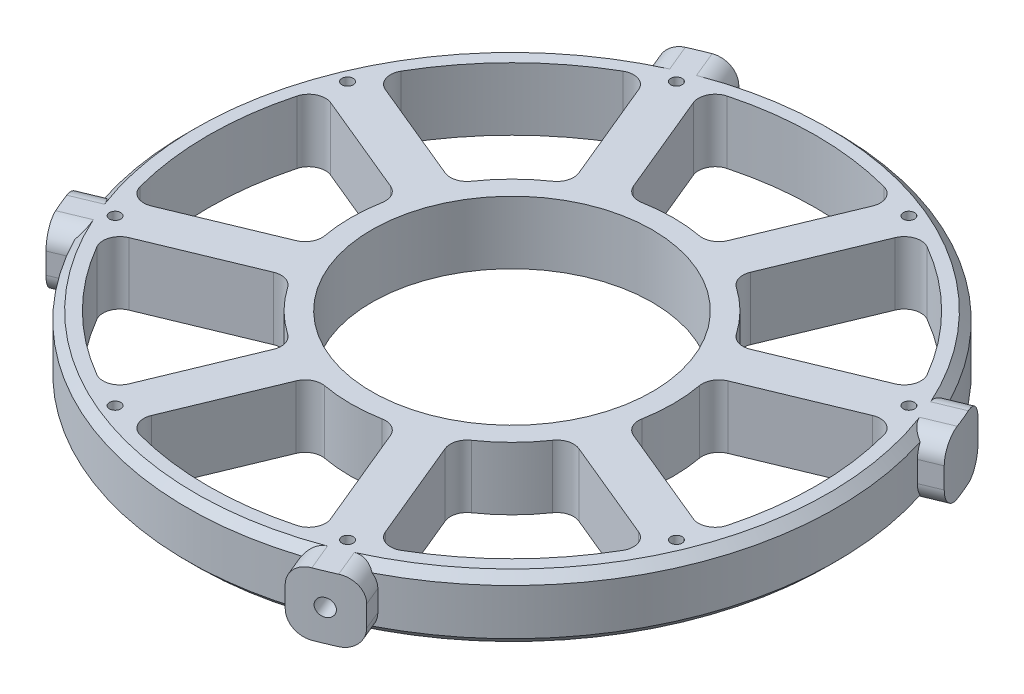
SolidWorks part; units mm, degrees
material "6061-T6 (SS)"
ref_plane "Front Plane" through (0, 0, 0) normal (0, 0, 1) x (1, 0, 0)
ref_plane "Top Plane" through (0, 0, 0) normal (0, 1, 0) x (1, 0, 0)
ref_plane "Right Plane" through (0, 0, 0) normal (1, 0, 0) x (0, 0, -1)
sketch "Sketch2" plane through (0, 0, 0) normal (1, 0, 0) x (0, 0, -1)
  line L0 (0, 0) -> (-77.55, 0)
  line L1 (-77.55, 0) -> (-77.55, 15)
  line L2 (-77.55, 15) -> (0, 15)
  line L5 (0, 15) -> (0, 0)
  dimension "D1" = 77.55
  dimension "D2" = 15
ref_axis "Axis1" through (0, -1.0933, 0) along (0, 1, 0)
revolve "Revolve1" add sketch "Sketch2" angle 360 about axis through (0, -1.0933, 0) along (0, 1, 0)
hole_wizard "#6-32 Tapped Hole2" positions "Sketch6" profile "Sketch7" tap size "#6-32" standard "ANSI Inch" end condition through all
sketch "Sketch6" plane through (0, 15, 0) normal (0, 1, 0) x (1, 0, 0)
  line L0 (0, 0) -> (-53.438, 129.0108) construction
  line L2 (0, 0) -> (0, 109.0908) construction
  point P0 (-27.7637, 67.0275)
  dimension "D1" = 22.5
  dimension "D2" = 72.55
sketch "Sketch7" plane through (-27.7637, 15, -67.0275) normal (1, 0, 0) x (0, 0, 1)
  line L0 (0, 0) -> (0, 15)
  line L1 (0, 15) -> (1.3525, 15)
  line L2 (1.3525, 15) -> (1.3525, 0)
  line L5 (1.3525, 0) -> (0, 0)
  line L11 (0, -6.35) -> (0, 107.95) construction
  dimension "Thread Major Dia." = 2.7051
  dimension "Thru Tap Drill Depth" = 15
pattern_circular "CirPattern3" count 8 over 360 about axis through (0, -1.0933, 0) along (0, 1, 0) of "#6-32 Tapped Hole2"
sketch "Sketch8" plane through (0, 15, 0) normal (0, 1, 0) x (1, 0, 0)
  line L4 (0, 0) -> (0, 93.9995) construction
  line L5 (0, 0) -> (113.8372, 0) construction
  line L6 (-9.9891, 37.1815) -> (-23.0783, 68.7815)
  line L7 (9.9891, 37.1815) -> (23.0783, 68.7815)
  line L8 (0, 0) -> (-27.7637, 67.0275) construction
  arc A0 (-9.9891, 37.1815) -> (9.9891, 37.1815) centre (0, 0) cw
  arc A1 (-23.0783, 68.7815) -> (23.0783, 68.7815) centre (0, 0) cw
  circle A2 centre (0, 0) radius 77.55 construction
  dimension "D1" = 38.5
  dimension "D2" = 5
  dimension "D3" = 5
extrude "Cut-Extrude1" cut sketch "Sketch8" against normal through all
fillet "Fillet1" radius 4 4 edges at (9.9891, 7.5, -37.1815) (23.0783, 7.5, -68.7815) (-9.9891, 7.5, -37.1815) (-23.0783, 7.5, -68.7815)
pattern_circular "CirPattern4" count 8 over 360 about axis through (0, -1.0933, 0) along (0, 1, 0) of "Cut-Extrude1", "Fillet1"
sketch "Sketch12" plane through (0, 15, 0) normal (0, 1, 0) x (1, 0, 0)
  line L0 (0, 0) -> (-27.7637, 67.0275) construction
  line L1 (-22.6569, 74.1665) -> (-24.5321, 78.6935)
  line L2 (-38.2979, 72.9915) -> (-36.4227, 68.4645)
  circle A0 centre (0, 0) radius 77.55 construction
  arc A1 (-24.5321, 78.6935) -> (-38.2979, 72.9915) centre (0, 0) ccw
  circle A2 centre (0, 0) radius 77.55 construction
  arc A3 (-36.4227, 68.4645) -> (-22.6569, 74.1665) centre (0, 0) cw
  dimension "D1" = 14.9
  dimension "D2" = 4.9
extrude "Boss-Extrude1" add sketch "Sketch12" against normal blind 15
fillet "Fillet2" radius 5 4 edges at (-23.5945, 15, -76.43) (-37.3603, 15, -70.728) (-23.5945, 0, -76.43) (-37.3603, 0, -70.728)
pattern_circular "CirPattern5" count 4 over 360 about axis through (0, -1.0933, 0) along (0, 1, 0) of "Fillet2", "Boss-Extrude1"
chamfer "Chamfer1" distance 2 angle 45 8 edges at (71.6469, 0, 29.6771) (-29.6771, 0, 71.6469) (-71.6469, 0, -29.6771) (-71.6469, 15, -29.6771) (-29.6771, 15, 71.6469) (71.6469, 15, 29.6771) (29.6771, 0, -71.6469) (29.6771, 15, -71.6469)
ref_plane "Plane1" through (0, 0, 0) normal (0.3827, 0, 0.9239) x (0, 1, 0)
hole_wizard "#20 (0.161) Diameter Hole1" positions "Sketch16" profile "Sketch15" hole size "#20" standard "ANSI Inch" end condition through all
sketch "Sketch16" plane through (0, 0, 0) normal (0.3827, 0, 0.9239) x (0, 1, 0)
  point P0 (7.5, 0)
  dimension "D1" = 7.5
sketch "Sketch15" plane through (0, 7.5, 0) normal (0, 1, 0) x (-0.9239, 0, 0.3827)
  line L0 (0, 0) -> (0, 103.1885)
  line L1 (0, 103.1885) -> (2.0447, 103.1885)
  line L2 (2.0447, 103.1885) -> (2.0447, 0)
  line L5 (2.0447, 0) -> (0, 0)
  line L11 (0, -6.35) -> (0, 107.95) construction
  dimension "Thru Hole Dia." = 4.0894
  dimension "Thru Hole Depth" = 103.1885
sketch "Sketch18" plane through (0, 0, 0) normal (0, -1, 0) x (1, 0, 0)
  circle A0 centre (0, 0) radius 33.5
  arc A1 (21.9315, -31.6427) -> (31.6427, -21.9315) centre (0, 0) ccw construction
  dimension "D1" = 5
extrude "Cut-Extrude2" cut sketch "Sketch18" against normal through all
equation "\"TubeDiameter\" = 6.500in"
equation "\"D1@Sketch2\"=(\"TubeDiameter\"/2)-5mm"
equation "\"D2@Sketch6\"=\"TubeDiameter\"/2-10mm"
